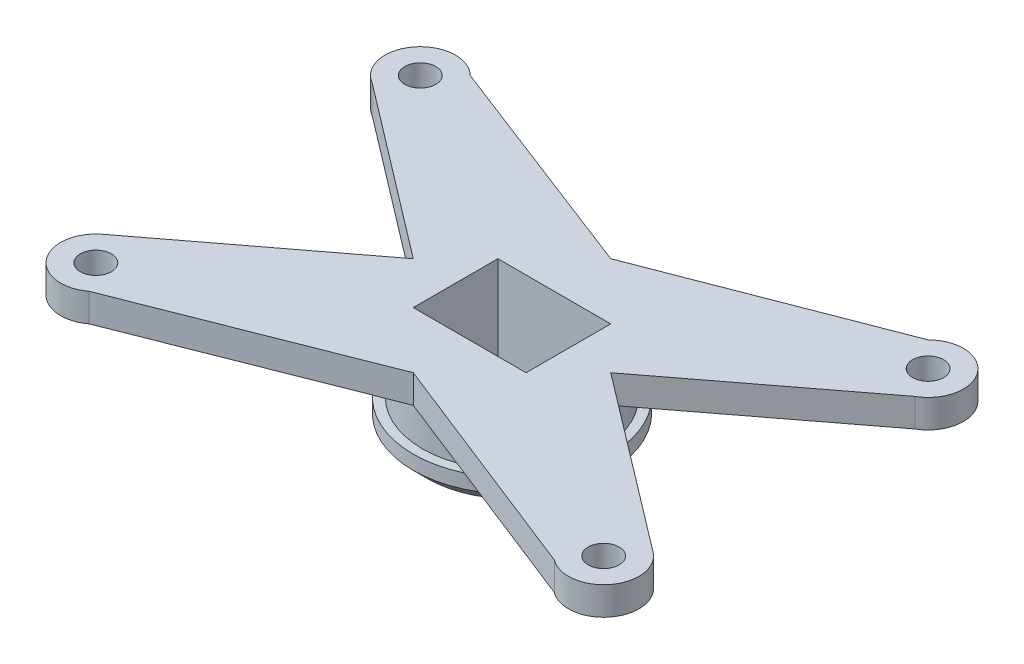
SolidWorks part; units mm, degrees
ref_plane "Front Plane" through (0, 0, 0) normal (0, 0, 1) x (1, 0, 0)
ref_plane "Top Plane" through (0, 0, 0) normal (0, 1, 0) x (1, 0, 0)
ref_plane "Right Plane" through (0, 0, 0) normal (1, 0, 0) x (0, 0, -1)
sketch "Sketch1" plane through (0, 0, 0) normal (0, 1, 0) x (1, 0, 0)
  circle A0 centre (0, 0) radius 6.35
  dimension "D1" = 12.7
extrude "Boss-Extrude1" add sketch "Sketch1" against normal blind 2
sketch "Sketch2" plane through (0, 0, 0) normal (0, 1, 0) x (1, 0, 0)
  circle A0 centre (0, 0) radius 7
  dimension "D1" = 14
extrude "Boss-Extrude2" add sketch "Sketch2" along normal blind 2
extrude "Boss-Extrude3" add sketch "Sketch2<2>" against normal blind 2 from surface starting at face at (0, -2, 6.35)
sketch "Sketch2<2>" plane through (0, 0, 0) normal (0, 1, 0) x (1, 0, 0) same geometry as "Sketch2"
chamfer "Chamfer1" distance 1 angle 45 2 edges at (0, 0, 7) (0, -4, 7)
sketch "Sketch3" plane through (0, -4, 0) normal (0, -1, 0) x (1, 0, 0)
  line L1 (-4, -3) -> (4, -3)
  line L2 (-4, -3) -> (-4, 3)
  line L3 (-4, 3) -> (4, 3)
  line L4 (4, -3) -> (4, 3)
  line L5 (-4, -3) -> (4, 3) construction
  line L6 (-4, 3) -> (4, -3) construction
  point P0 (0, 0)
  dimension "D1" = 8
  dimension "D2" = 6
extrude "Cut-Extrude1" cut sketch "Sketch3" against normal through all
sketch "Sketch4" plane through (0, 2, 0) normal (0, 1, 0) x (1, 0, 0)
  line L0 (0, 0) -> (0, 14) construction
  line L1 (0, 0) -> (20.3185, 0) construction
  line L2 (20.5, 14) -> (-20.5, 14)
  line L3 (-20.5, 14) -> (-20.5, -14)
  line L4 (-20.5, -14) -> (20.5, -14)
  line L5 (20.5, -14) -> (20.5, 14)
  circle A0 centre (-18, 11.5) radius 1.1
  circle A1 centre (-18, -11.5) radius 1.1
  circle A2 centre (18, -11.5) radius 1.1
  circle A3 centre (18, 11.5) radius 1.1
  point P9 (0, 14)
  point P17 (0, 0)
  point P18 (0, 0)
  point P19 (0, 0)
  dimension "D4" = 36
  dimension "D5" = 2.2
  dimension "D6" = 23
  dimension "D7" = 2.5
  dimension "D8" = 2.5
  dimension "D1" = 41
  dimension "D2" = 28
  dimension "D3" = 14
sketch "Sketch6" plane through (0, 2, 0) normal (0, 1, 0) x (1, 0, 0)
  circle A0 centre (-18, 11.5) radius 1.1
  circle A1 centre (18, 11.5) radius 1.1
  circle A2 centre (18, -11.5) radius 1.1
  circle A3 centre (-18, -11.5) radius 1.1
  circle A4 centre (-18, -11.5) radius 2.5
  circle A5 centre (18, -11.5) radius 2.5
  circle A6 centre (18, 11.5) radius 2.5
  circle A7 centre (-18, 11.5) radius 2.5
  dimension "D1" = 5
  dimension "D2" = 2.2
extrude "Boss-Extrude4" add sketch "Sketch6" along normal blind 1 and the other way blind 1 separate body
sketch "Sketch7" plane through (0, 3, 0) normal (0, 1, 0) x (1, 0, 0)
  line L2 (-16.2322, 13.2678) -> (0, 7)
  line L3 (0, 0) -> (0, 14) construction
  line L4 (0, 7) -> (16.2322, 13.2678)
  line L6 (19.7678, 9.7322) -> (7, 0)
  line L7 (0, 0) -> (20.3185, 0) construction
  line L8 (-19.7678, 9.7322) -> (-7, 0)
  line L9 (-7, 0) -> (-19.5127, -9.5096)
  line L11 (-16.4873, -13.4904) -> (0, -7)
  line L12 (0, -7) -> (16.4873, -13.4904)
  line L14 (19.5127, -9.5096) -> (7, 0)
  line L15 (-19.7678, 9.7322) -> (-18, 9)
  line L16 (-18, 9) -> (-15.5, 11.5)
  line L17 (-15.5, 11.5) -> (-16.2322, 13.2678)
  line L18 (-19.5127, -9.5096) -> (-18, -9)
  line L19 (-18, -9) -> (-15.5, -11.5)
  line L20 (-15.5, -11.5) -> (-16.4873, -13.4904)
  line L21 (16.4873, -13.4904) -> (15.5, -11.5)
  line L22 (15.5, -11.5) -> (18, -9)
  line L23 (18, -9) -> (19.5127, -9.5096)
  line L24 (16.2322, 13.2678) -> (15.5, 11.5)
  line L25 (15.5, 11.5) -> (18, 9)
  line L26 (18, 9) -> (19.7678, 9.7322)
  line L28 (-4, -3) -> (4, -3)
  line L29 (-4, -3) -> (-4, 3)
  line L30 (-4, 3) -> (4, 3)
  line L31 (4, -3) -> (4, 3)
  line L32 (-4, -3) -> (4, 3) construction
  line L33 (-4, 3) -> (4, -3) construction
  circle A0 centre (-18, 11.5) radius 2.5 construction
  circle A1 centre (18, 11.5) radius 2.5 construction
  circle A2 centre (0, 0) radius 7 construction
  circle A3 centre (-18, -11.5) radius 2.5 construction
  circle A4 centre (18, -11.5) radius 2.5 construction
  point P34 (0, 0)
extrude "Boss-Extrude5" add sketch "Sketch7" against normal up to surface (2 mm away) up to face at (-18, 1, -10.4)
